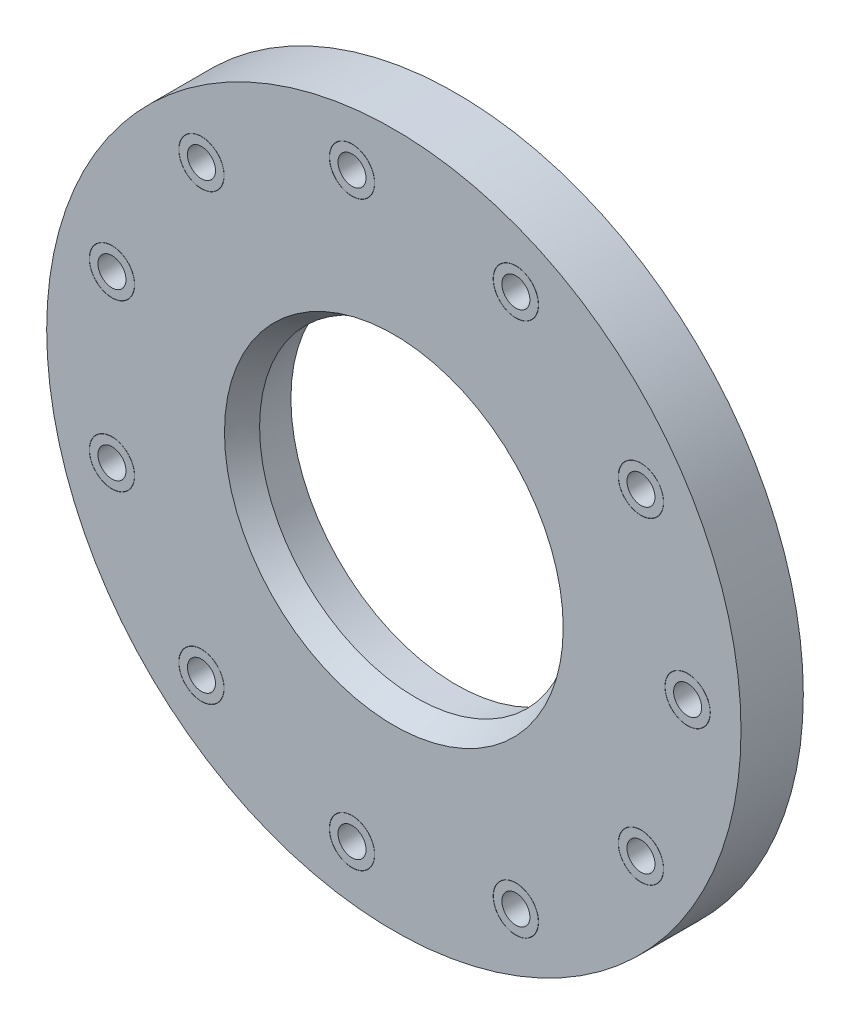
SolidWorks part; units mm, degrees
ref_plane "Front Plane" through (0, 0, 0) normal (0, 0, 1) x (1, 0, 0)
ref_plane "Top Plane" through (0, 0, 0) normal (0, 1, 0) x (1, 0, 0)
ref_plane "Right Plane" through (0, 0, 0) normal (1, 0, 0) x (0, 0, -1)
ref_plane "Plane1" through (0, 0, 15) normal (0, 0, 1) x (1, 0, 0)
sketch "Sketch1" plane through (0, 0, 15) normal (0, 0, 1) x (1, 0, 0)
  circle A0 centre (0, 0) radius 39
  circle A1 centre (0, 0) radius 33 construction
  circle A2 centre (33, 0) radius 2.55
  circle A3 centre (27.7614, -17.8411) radius 2.55
  circle A4 centre (13.7087, -30.0179) radius 2.55
  circle A5 centre (-4.6964, -32.6641) radius 2.55
  circle A6 centre (-21.6104, -24.9397) radius 2.55
  circle A7 centre (-31.6633, -9.2972) radius 2.55
  circle A8 centre (-31.6633, 9.2972) radius 2.55
  circle A9 centre (-21.6104, 24.9397) radius 2.55
  circle A10 centre (-4.6964, 32.6641) radius 2.55
  circle A11 centre (13.7087, 30.0179) radius 2.55
  circle A12 centre (27.7614, 17.8411) radius 2.55
  circle A13 centre (0, 0) radius 16.025
  point P28 (0, 0)
extrude "Boss-Extrude1" add sketch "Sketch1" along normal blind 7
sketch "Sketch2" plane through (0, 0, 15) normal (0, 0, -1) x (-1, 0, 0)
  circle A0 centre (0, 0) radius 18.5625
  dimension "D1" = 37.125
extrude "Cut-Extrude1" cut sketch "Sketch2" against normal blind 4.5
sketch "Sketch3" plane through (0, 0, 22) normal (0, 0, 1) x (1, 0, 0)
  circle A0 centre (-4.6964, 32.6641) radius 1.575
  circle A1 centre (-4.6964, 32.6641) radius 2.525
  circle A2 centre (13.7087, 30.0179) radius 2.525
  circle A3 centre (13.7087, 30.0179) radius 1.575
  circle A4 centre (27.7614, 17.8411) radius 2.525
  circle A5 centre (27.7614, 17.8411) radius 1.575
  circle A6 centre (33, 0) radius 2.525
  circle A7 centre (33, 0) radius 1.575
  circle A8 centre (27.7614, -17.8411) radius 2.525
  circle A9 centre (27.7614, -17.8411) radius 1.575
  circle A10 centre (13.7087, -30.0179) radius 2.525
  circle A11 centre (13.7087, -30.0179) radius 1.575
  circle A12 centre (-4.6964, -32.6641) radius 2.525
  circle A13 centre (-4.6964, -32.6641) radius 1.575
  circle A14 centre (-21.6104, -24.9397) radius 2.525
  circle A15 centre (-21.6104, -24.9397) radius 1.575
  circle A16 centre (-31.6633, -9.2972) radius 2.525
  circle A17 centre (-31.6633, -9.2972) radius 1.575
  circle A18 centre (-31.6633, 9.2972) radius 2.525
  circle A19 centre (-31.6633, 9.2972) radius 1.575
  circle A20 centre (-21.6104, 24.9397) radius 2.525
  circle A21 centre (-21.6104, 24.9397) radius 1.575
  point P36 (0, 0)
  dimension "D1" = 5.05
  dimension "D2" = 3.15
  dimension "D3" = 11
extrude "Boss-Extrude2" add sketch "Sketch3" against normal blind 4
chamfer "Chamfer1" distance 3 angle 60 1 edges at (16.025, 0, 22) first distance on face at (30.3114, 17.8411, 22)
chamfer "Chamfer3" distance 0.5 angle 45 11 edges at (35.55, 0, 15) (30.3114, -17.8411, 15) (16.2587, -30.0179, 15) (-2.1464, -32.6641, 15) (-19.0604, -24.9397, 15) (-29.1133, -9.2972, 15) (-29.1133, 9.2972, 15) (-19.0604, 24.9397, 15) (-2.1464, 32.6641, 15) (16.2587, 30.0179, 15) (30.3114, 17.8411, 15)
equation "\"RingPinShaft\"= 5.05"
equation "\"CenterBearingOut\"=32.05"
equation "\"OutputBearingOut\"=37.05"
equation "\"RingPostIn\"=5.15"
equation "\"CamBearingOut\"=15.1"
equation "\"DiskOutputShaft\"=10.1"
equation "\"CenterShaft\"=25.2"
equation "\"Eccentricity\"=2"
equation "\"CycCamShaft\"=10.05"
equation "\"m3Thru\"=3.15"
equation "\"m3Insert\"=4.2"
equation "\"D1@Sketch3\"=\"RingPinShaft\""
equation "\"D2@Sketch3\"=\"m3Thru\""
